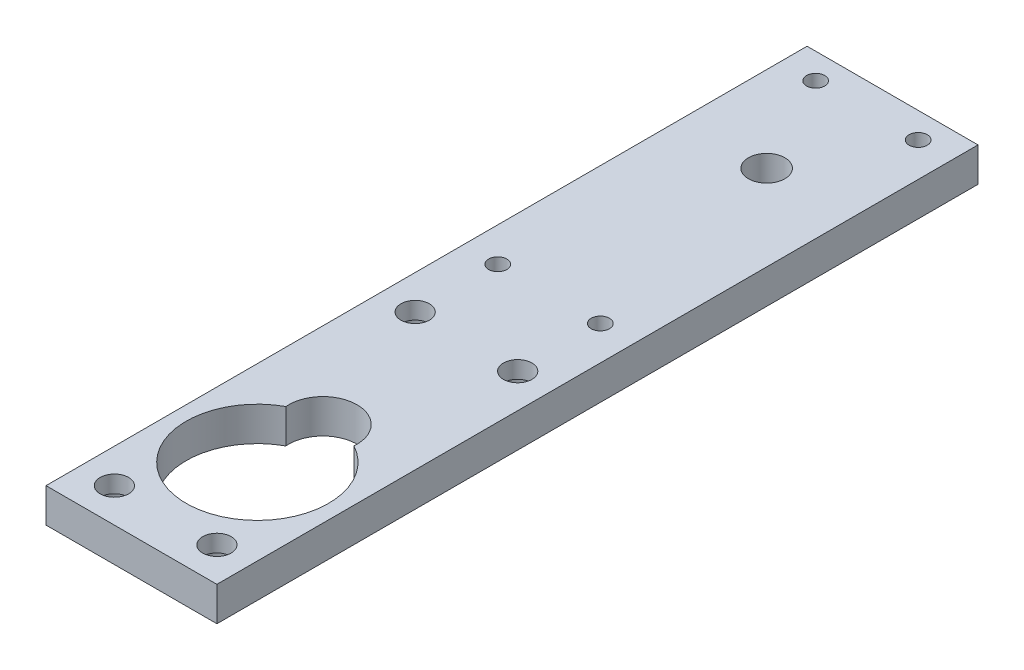
SolidWorks part; units mm, degrees
ref_plane "前视基准面" through (0, 0, 0) normal (0, 0, 1) x (1, 0, 0)
ref_plane "上视基准面" through (0, 0, 0) normal (0, 1, 0) x (1, 0, 0)
ref_plane "右视基准面" through (0, 0, 0) normal (1, 0, 0) x (0, 0, -1)
other "Configuration Table"
sketch "草图1" plane through (0, 0, 0) normal (0, 1, 0) x (1, 0, 0)
  line L1 (0, 0) -> (15, 0)
  line L2 (0, 0) -> (0, -32.4)
  line L3 (0, -32.4) -> (15, -32.4)
  line L4 (15, 0) -> (15, -32.4)
  line L9 (0, 2) -> (15, 2)
  line L10 (0, 2) -> (0, 34.4)
  line L11 (0, 34.4) -> (15, 34.4)
  line L12 (15, 2) -> (15, 34.4)
  line L17 (0, 0) -> (15, 0)
  line L18 (0, 0) -> (0, 2)
  line L19 (0, 2) -> (15, 2)
  line L20 (15, 0) -> (15, 2)
  circle A4 centre (3, -3) radius 1.25
  circle A5 centre (12, -3) radius 1.25
  circle A6 centre (3, -29.4) radius 1.25
  circle A7 centre (12, -29.4) radius 1.25
  circle A8 centre (7.5, -21.35) radius 6.25
  circle A9 centre (7.5, -15.6) radius 3
  circle A10 centre (3, -3) radius 2
  circle A11 centre (12, -3) radius 2
  circle A12 centre (3, -29.4) radius 2
  circle A13 centre (12, -29.4) radius 2
  circle A22 centre (3, 4.25) radius 1.3
  circle A23 centre (12, 4.25) radius 1.3
  circle A24 centre (3, 32.15) radius 1.3
  circle A25 centre (12, 32.15) radius 1.3
  circle A26 centre (3, 32.15) radius 0.8
  circle A27 centre (12, 32.15) radius 0.8
  circle A28 centre (3, 4.25) radius 0.8
  circle A29 centre (12, 4.25) radius 0.8
  circle A30 centre (7.5, 23.35) radius 1.6
  point P10 (7.5, -32.4)
  point P38 (0, 0)
  point P39 (0, 0)
  point P40 (0, 0)
  point P41 (0, 0)
  point P42 (7.5, 30.5243)
  dimension "D3" = 2.5
  dimension "D8" = 4
  dimension "D6" = 12.5
  dimension "D7" = 6
  dimension "D12" = 2.6
  dimension "D13" = 1.6
  dimension "D14" = 3.2
  dimension "D1" = 3
  dimension "D2" = 15
  dimension "D4" = 11.05
  dimension "D5" = 5.75
  dimension "D9" = 3
  dimension "D10" = 3
  dimension "D11" = 3
  dimension "32.4" = 32.4
  dimension "D15" = 3
  dimension "D16" = 2.25
  dimension "D17" = 3
  dimension "D18" = 27.9
  dimension "D19" = 11.05
  dimension "D20" = 2
extrude "凸台-拉伸1" add sketch "草图1" along normal blind 3 contours L4 L3 L2 L1 | L20 L19 L18 L17 | L12 L11 L10 L9 | A4 | A5 | A9 | A8 | A6 | A7 | A28 | A29 | A30 | A26 | A27
extrude "切除-拉伸3" cut sketch "草图1<5>" along normal blind 1.5 contours A11 | A10 | A12 | A13 | A23 | A25 | A24 | A22
sketch "草图1<5>" plane through (0, 0, 0) normal (0, 1, 0) x (1, 0, 0) same geometry as "草图1"
